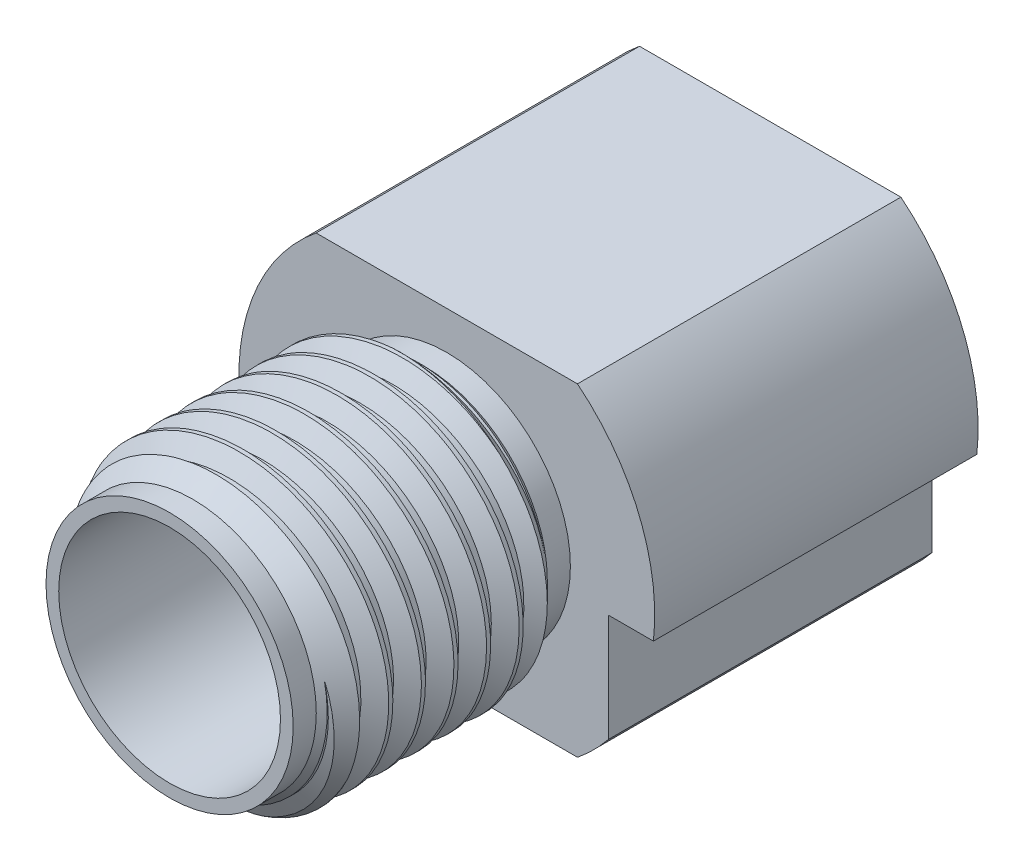
SolidWorks part; units mm, degrees
ref_plane "Front Plane" through (0, 0, 0) normal (0, 0, 1) x (1, 0, 0)
ref_plane "Top Plane" through (0, 0, 0) normal (0, 1, 0) x (1, 0, 0)
ref_plane "Right Plane" through (0, 0, 0) normal (1, 0, 0) x (0, 0, -1)
sketch "Sketch1" plane through (0, 0, 0) normal (0, 0, 1) x (1, 0, 0)
  line L0 (-2.8284, 3.5) -> (2.8284, 3.5)
  line L1 (-2.8284, -3.5) -> (2.8284, -3.5)
  line L2 (0, 0) -> (4.5, 0) construction
  line L3 (-4.4721, -0.5) -> (-3.5, -0.5)
  line L4 (-3.5, -0.5) -> (-3.5, -2.8284)
  line L5 (0, 0) -> (0, -4.5) construction
  line L6 (4.4721, -0.5) -> (3.5, -0.5)
  line L7 (3.5, -0.5) -> (3.5, -2.8284)
  arc A0 (2.8284, -3.5) -> (3.5, -2.8284) centre (0, 0) ccw
  arc A1 (-2.8284, -3.5) -> (0, -4.5) centre (0, 0) ccw construction
  arc A2 (0, -4.5) -> (2.8284, -3.5) centre (0, 0) ccw construction
  arc A3 (4.4721, -0.5) -> (2.8284, 3.5) centre (0, 0) ccw
  arc A4 (3.5, -2.8284) -> (4.4721, -0.5) centre (0, 0) ccw construction
  arc A5 (-3.5, -2.8284) -> (-2.8284, -3.5) centre (0, 0) ccw
  arc A6 (-4.4721, -0.5) -> (-3.5, -2.8284) centre (0, 0) ccw construction
  arc A7 (-2.8284, 3.5) -> (-4.4721, -0.5) centre (0, 0) ccw
  arc A8 (2.8284, 3.5) -> (-2.8284, 3.5) centre (0, 0) ccw construction
  dimension "D1" = 9
  dimension "D2" = 7
  dimension "D3" = 3
  dimension "D4" = 7
extrude "Boss-Extrude1" add sketch "Sketch1" along normal blind 7
sketch "Sketch2" plane through (0, 0, 0) normal (0, 0, -1) x (-1, 0, 0)
  line L0 (-1.5559, -5.2706) -> (2.5772, -5.2706) construction
  circle A0 centre (0, 0) radius 1.85
  dimension "D1" = 3.7
extrude "Cut-Extrude1" cut sketch "Sketch2" against normal blind 0.05
sketch "Sketch3" plane through (0, 0, 0.05) normal (0, 0, -1) x (-1, 0, 0)
  circle A0 centre (0, 0) radius 0.38
  dimension "D1" = 0.76
extrude "Boss-Extrude2" add sketch "Sketch3" along normal blind 2
chamfer "Chamfer1" distance 0.1 angle 45 1 edges at (-0.38, 0, -1.95)
sketch "Sketch4" plane through (0, 0, 7) normal (0, 0, 1) x (1, 0, 0)
  circle A0 centre (0, 0) radius 2.675
  circle A1 centre (0, 0) radius 2.4
  dimension "D1" = 5.35
  dimension "D2" = 4.8
extrude "Boss-Extrude3" add sketch "Sketch4" along normal blind 6
sketch "Sketch10" plane through (0, 0, 0) normal (1, 0, 0) x (0, 0, -1)
  line L0 (-12.5, 2.675) -> (-12, 3.175)
  line L1 (-7, 2.675) -> (-13, 2.675) construction
  line L2 (-12, 3.175) -> (-8, 3.175)
  line L3 (-8, 3.175) -> (-7.5, 2.675)
  line L4 (-7.5, 2.675) -> (-12.5, 2.675)
  line L5 (-13, 0) -> (-7.2734, 0) construction
  line L6 (-13, 2.675) -> (-13, -2.675) construction
  line L7 (-7, 3.5) -> (-7, -0.5) construction
  dimension "D1" = 6.35
  dimension "D2" = 0.5
  dimension "D3" = 0.5
  dimension "D4" = 45
revolve "Revolve1" add sketch "Sketch10" angle 360 about L5
thread "Thread1" pitch 0.7056 method cut profile "Thread Profile2" start angle 0, offset 0.8, length 10, pitch 0.7056, diameter 6.35
ref_plane "Plane2" through (3.175, 0, 7.2) normal (0, -1, 0) x (1, 0, 0)
sketch "Thread Profile2" plane through (3.175, 0, 7.2) normal (0, -1, 0) x (1, 0, 0)
  line L0 (0, 0) -> (0, 0.7056) construction
  line L11 (0, 0) -> (0, 0.6174)
  line L12 (0, 0.6174) -> (-0.3819, 0.3969)
  line L13 (-0.3819, 0.3969) -> (-0.3819, 0.2205)
  line L15 (-0.3819, 0.2205) -> (0, 0)
  line L17 (-0.3819, 0.3087) -> (0, 0.3087) construction
  point P2 (0, 0)
  dimension "Pitch" = 0.7056
  dimension "Profile_Angle" = 60
  dimension "Profile_Land" = 0.1764
  dimension "Profile_Height" = 0.3819
